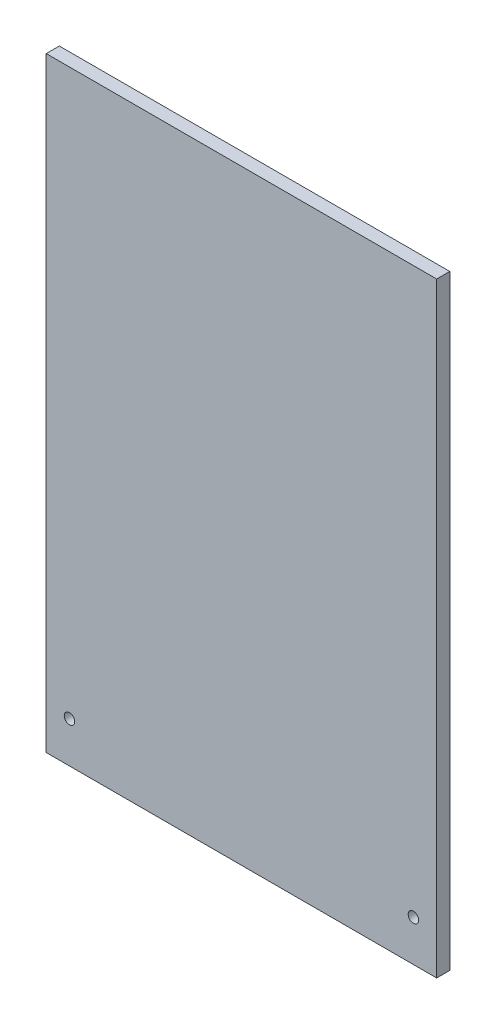
SolidWorks part; units mm, degrees
ref_plane "Спереди" through (0, 0, 0) normal (0, 0, 1) x (1, 0, 0)
ref_plane "Сверху" through (0, 0, 0) normal (0, 1, 0) x (1, 0, 0)
ref_plane "Справа" through (0, 0, 0) normal (1, 0, 0) x (0, 0, -1)
sketch "Sketch1" plane through (0, 0, 0) normal (0, 0, 1) x (1, 0, 0)
  line L1 (-64.2, 185) -> (64.2, 185) construction
  line L6 (59.8, 175) -> (59.8, 185) construction
  line L11 (-59.6, 0) -> (59.6, 0)
  line L12 (-59.6, 0) -> (-59.6, 184.8)
  line L13 (-59.6, 184.8) -> (59.6, 184.8)
  line L14 (59.6, 0) -> (59.6, 184.8)
  circle A0 centre (52.5, 12.5) radius 1.6
  circle A1 centre (-52.5, 12.5) radius 1.6
  point P17 (0, 0)
  dimension "D2" = 3.2
  dimension "D1" = 0.2
  dimension "D3" = 0.2
extrude "Extrude1" add sketch "Sketch1" along normal blind 4
equation "\"thickness\"=4"
equation "\"D1@Extrude1\"=\"thickness\""
